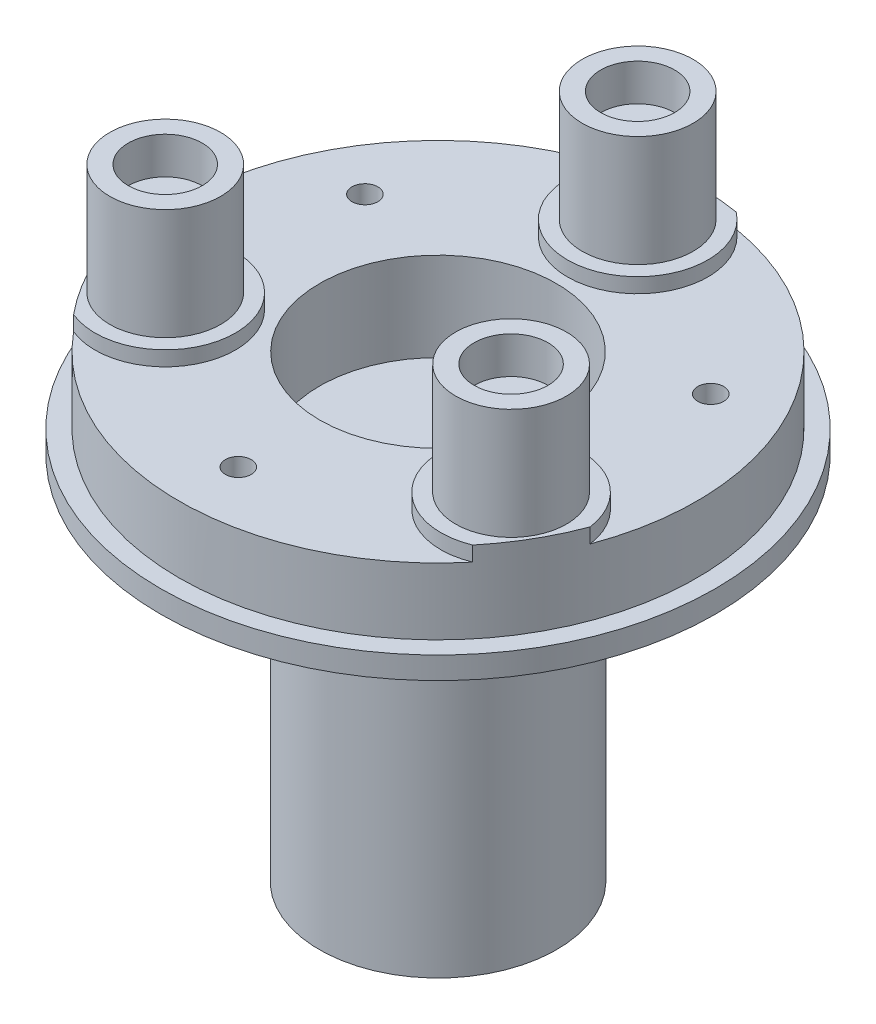
SolidWorks part; units mm, degrees
ref_plane "Front Plane" through (0, 0, 0) normal (0, 0, 1) x (1, 0, 0)
ref_plane "Top Plane" through (0, 0, 0) normal (0, 1, 0) x (1, 0, 0)
ref_plane "Right Plane" through (0, 0, 0) normal (1, 0, 0) x (0, 0, -1)
sketch "Sketch1" plane through (0, 0, 0) normal (0, 1, 0) x (1, 0, 0)
  line L0 (0, 0) -> (0, 44.6523) construction
  circle A4 centre (0, 0) radius 37.5
  circle A5 centre (0, 0) radius 35
  arc A6 (-10.4425, 33.4059) -> (10.4425, 33.4059) centre (0, 30) ccw
  circle A7 centre (0, 0) radius 35
  arc A8 (34.1516, -7.6594) -> (23.7091, -25.7465) centre (25.9808, -15) ccw
  arc A9 (-23.7091, -25.7465) -> (-34.1516, -7.6594) centre (-25.9808, -15) ccw
  point P17 (0, 0)
  dimension "D1" = 75
  dimension "D2" = 70
  dimension "D3" = 30
  dimension "D4" = 3
extrude "Boss-Extrude1" add sketch "Sketch1" along normal blind 3 contours A4
extrude "Boss-Extrude2" add sketch "Sketch1<3>" along normal blind 12 contours A5
sketch "Sketch1<3>" plane through (0, 0, 0) normal (0, 1, 0) x (1, 0, 0) same geometry as "Sketch1"
sketch "Sketch13" plane through (0, 12, 0) normal (0, 1, 0) x (1, 0, 0)
  circle A0 centre (0, 0) radius 16
  dimension "D1" = 32
extrude "Cut-Extrude6" cut sketch "Sketch13" against normal through all
sketch "Sketch24" plane through (0, 12, 0) normal (0, 1, 0) x (1, 0, 0)
  line L0 (0, 0) -> (0, 27.027) construction
  arc A0 (-5.813, 34.5139) -> (5.813, 34.5139) centre (0, 27) ccw
  circle A1 centre (0, 0) radius 35
  arc A2 (32.7964, -12.2227) -> (26.9834, -22.2912) centre (23.3827, -13.5) ccw
  arc A3 (-26.9834, -22.2912) -> (-32.7964, -12.2227) centre (-23.3827, -13.5) ccw
  point P15 (0, 0)
  circle M8 centre (0, 0) radius 35
  dimension "D1" = 19
  dimension "D4" = 70
  dimension "D2" = 27
  dimension "D3" = 3
extrude "Boss-Extrude9" add sketch "Sketch24" along normal blind 2 contours A1 A3 | A0 M8 | A1 A2 region at (0, 12, -26.6249) region at (-23.0578, 12, 13.3124) region at (23.0578, 12, 13.3124)
sketch "Sketch25" plane through (0, 14, 0) normal (0, 1, 0) x (1, 0, 0)
  line L0 (0, 0) -> (0, 55.8426) construction
  circle A0 centre (0, 27) radius 7.5
  circle A1 centre (23.3827, -13.5) radius 7.5
  circle A2 centre (-23.3827, -13.5) radius 7.5
  point P11 (0, 0)
  dimension "D2" = 15
  dimension "D1" = 27
  dimension "D3" = 3
extrude "Boss-Extrude10" add sketch "Sketch25" along normal blind 15
sketch "Sketch26" plane through (0, 29, 0) normal (0, 1, 0) x (1, 0, 0)
  line L0 (0, 0) -> (0, 38.3857) construction
  circle A0 centre (0, 27) radius 5
  circle A1 centre (23.3827, -13.5) radius 5
  circle A2 centre (-23.3827, -13.5) radius 5
  point P11 (0, 0)
  dimension "D2" = 10
  dimension "D1" = 27
  dimension "D3" = 3
extrude "Cut-Extrude9" cut sketch "Sketch26" against normal blind 5
hole_wizard "CBORE for M3 Pan Head Machine Screw1" positions "Sketch27" profile "Sketch28" counterbore size "M3" standard "ANSI Metric" end condition through all
sketch "Sketch27" plane through (0, 0, 0) normal (0, -1, 0) x (-1, 0, 0)
  point P0 (0, 27)
  point P9 (23.3827, -13.5)
  point P10 (-23.3827, -13.5)
  dimension "D1" = 27
  dimension "D2" = 3
sketch "Sketch28" plane through (0, 0, -27) normal (1, 0, 0) x (0, 0, -1)
  line L0 (0, 0) -> (0, 29)
  line L1 (0, 29) -> (1.8, 29)
  line L3 (1.8, 29) -> (1.8, 2.4)
  line L4 (3.5, 2.4) -> (1.8, 2.4)
  line L5 (3.5, 2.4) -> (3.5, 0.025)
  line L6 (3.5, 0.025) -> (3.525, 0)
  line L7 (3.525, 0) -> (0, 0)
  line L8 (-3.5, 0.025) -> (-3.525, 0) construction
  line L11 (0, -6.35) -> (0, 107.95) construction
  dimension "Thru Hole Dia." = 3.6
  dimension "Thru Hole Depth" = 29
  dimension "C'Bore Dia." = 7
  dimension "C'Bore Depth" = 2.4
  dimension "Near C'Sink Dia." = 7.05
  dimension "Near C'Sink Angle" = 90
sketch "Sketch29" plane through (0, 12, 0) normal (0, 1, 0) x (1, 0, 0)
  line L0 (0, 0) -> (23.3827, 13.5) construction
  line L1 (0, 0) -> (0, 14.4601) construction
  circle A0 centre (23.3827, 13.5) radius 1.75
  circle A1 centre (0, -27) radius 1.75
  circle A2 centre (-23.3827, 13.5) radius 1.75
  point P11 (0, 0)
  dimension "D3" = 3.5
  dimension "D1" = 60
  dimension "D2" = 27
  dimension "D4" = 3
extrude "Cut-Extrude10" cut sketch "Sketch29" against normal through all
sketch "Sketch30" plane through (0, 12, 0) normal (0, -1, 0) x (1, 0, 0)
  circle A0 centre (0, 0) radius 16
sketch "Sketch31" plane through (0, 0, 0) normal (0, -1, 0) x (1, 0, 0)
  circle A0 centre (0, 0) radius 16.05
extrude "Boss-Extrude11" add sketch "Sketch31" along normal blind 50 separate body
